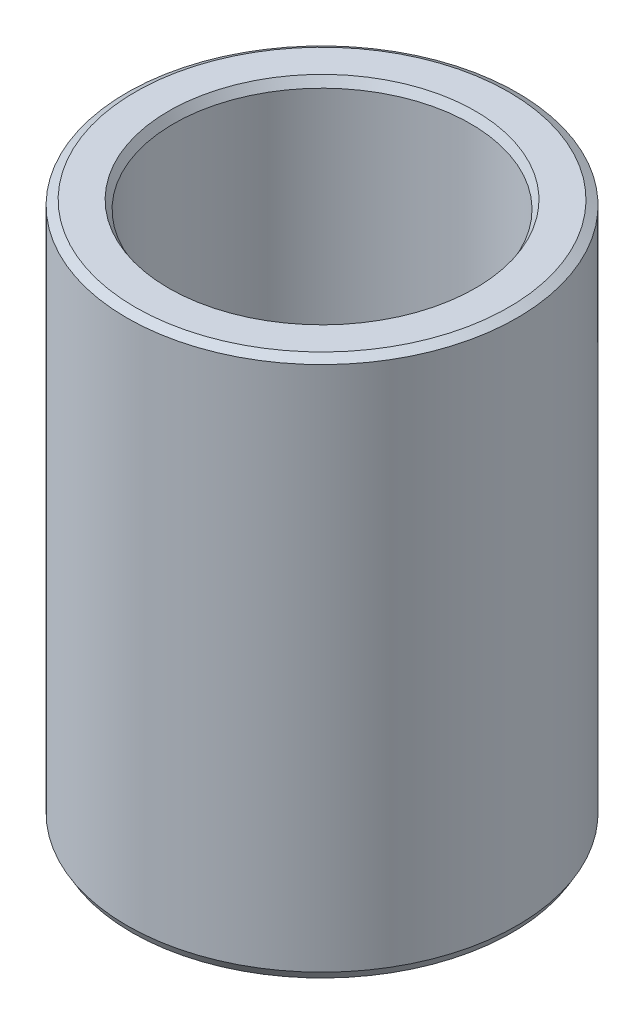
SolidWorks part; units mm, degrees
ref_plane "Front Plane" through (0, 0, 0) normal (0, 0, 1) x (1, 0, 0)
ref_plane "Top Plane" through (0, 0, 0) normal (0, 1, 0) x (1, 0, 0)
ref_plane "Right Plane" through (0, 0, 0) normal (1, 0, 0) x (0, 0, -1)
sketch "Sketch1" plane through (0, 0, 0) normal (0, 1, 0) x (1, 0, 0)
  circle A0 centre (0, 0) radius 45
  dimension "SLEEVE_OD" = 90
extrude "Boss-Extrude1" add sketch "Sketch1" along normal blind 124.4292
sketch "Sketch2" plane through (0, 0, 0) normal (0, 1, 0) x (1, 0, 0)
  circle A0 centre (0, 0) radius 34.2428
  dimension "BORE_D" = 68.4855
extrude "Cut-Extrude1" cut sketch "Sketch2" along normal through all
chamfer "Chamfer1" distance 1.1323 angle 60 4 edges at (0, 124.4292, 34.2428) (0, 0, 34.2428) (0, 0, 45) (0, 124.4292, 45) first distance on face at (0, 124.4292, 34.2428) first distance on face at (0, 0, 34.2428) first distance on face at (0, 124.4292, 45)
